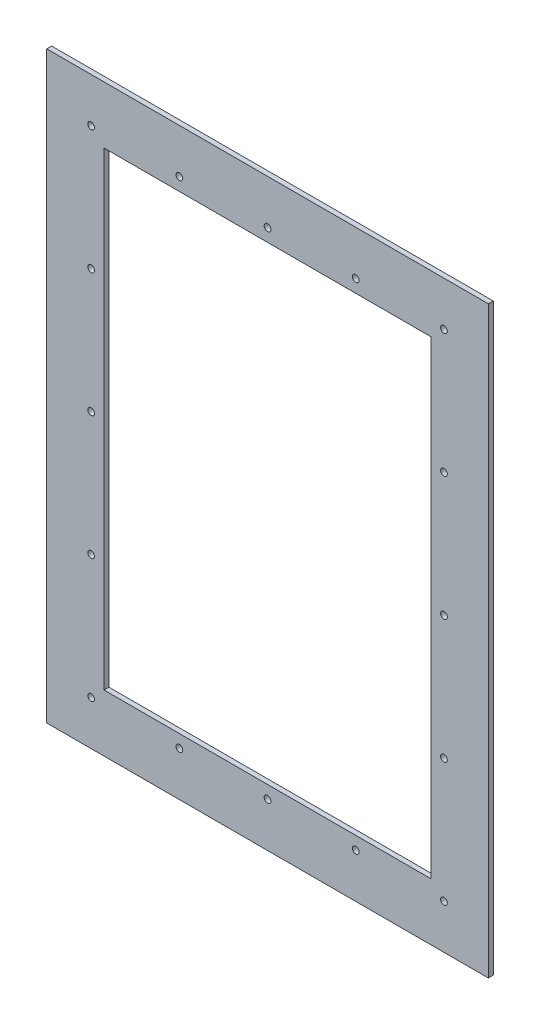
SolidWorks part; units mm, degrees
ref_plane "Front Plane" through (0, 0, 0) normal (0, 0, 1) x (1, 0, 0)
ref_plane "Top Plane" through (0, 0, 0) normal (0, 1, 0) x (1, 0, 0)
ref_plane "Right Plane" through (0, 0, 0) normal (1, 0, 0) x (0, 0, -1)
sketch "Sketch1" plane through (0, 0, 0) normal (0, 0, 1) x (1, 0, 0)
  line L0 (-100, 143.5) -> (100, -143.5) construction
  line L1 (-100, 143.5) -> (100, 143.5)
  line L2 (-100, 143.5) -> (-100, -143.5)
  line L3 (-100, -143.5) -> (100, -143.5)
  line L4 (100, 143.5) -> (100, -143.5)
  line L5 (-135, 178.5) -> (135, -178.5) construction
  line L6 (-135, 178.5) -> (135, 178.5)
  line L7 (-135, 178.5) -> (-135, -178.5)
  line L8 (-135, -178.5) -> (135, -178.5)
  line L9 (135, 178.5) -> (135, -178.5)
  line L10 (0, 143.5) -> (0, 178.5) construction
  line L11 (-100, 0) -> (-135, 0) construction
  line L12 (-100, 143.5) -> (-135, 178.5) construction
  line L13 (-53.9304, 151.3609) -> (0, 151.3609) construction
  line L14 (-107.8609, 151.3609) -> (-53.9304, 151.3609) construction
  line L15 (-107.8609, 151.3609) -> (-107.8609, 0) construction
  line L16 (0, 151.3609) -> (0, 143.5) construction
  line L17 (-107.8609, 0) -> (-100, 0) construction
  circle A0 centre (-107.8609, 151.3609) radius 2.05
  circle A1 centre (-53.9304, 151.3609) radius 2.05
  circle A2 centre (-107.8609, 75.6804) radius 2.05
  circle A3 centre (-53.9304, -151.3609) radius 2.05
  circle A4 centre (-107.8609, -151.3609) radius 2.05
  circle A5 centre (-107.8609, -75.6804) radius 2.05
  circle A6 centre (53.9304, 151.3609) radius 2.05
  circle A7 centre (107.8609, 151.3609) radius 2.05
  circle A8 centre (107.8609, 75.6804) radius 2.05
  circle A9 centre (53.9304, -151.3609) radius 2.05
  circle A10 centre (107.8609, -151.3609) radius 2.05
  circle A11 centre (107.8609, -75.6804) radius 2.05
  circle A12 centre (-107.8609, 0) radius 2.05
  circle A13 centre (107.8609, 0) radius 2.05
  circle A14 centre (0, 151.3609) radius 2.05
  circle A15 centre (0, -151.3609) radius 2.05
  point P42 (0, 151.6705)
  point P45 (-107.8609, 151.3609)
  dimension "D4" = 4.1
  dimension "D1" = 200
  dimension "D2" = 287
  dimension "D3" = 35
extrude "Boss-Extrude1" add sketch "Sketch1" along normal blind 3
